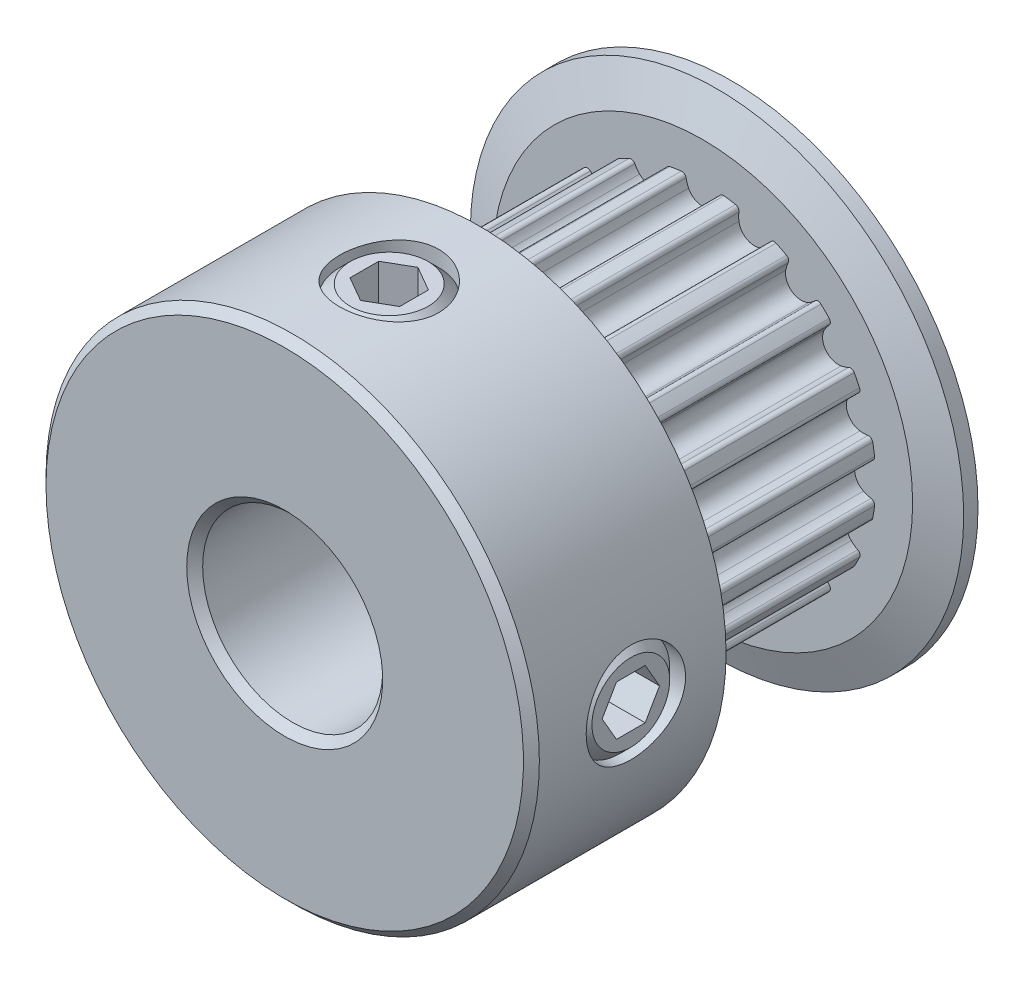
SolidWorks part; units mm, degrees
ref_plane "Front Plane" through (0, 0, 0) normal (0, 0, 1) x (1, 0, 0)
ref_plane "Top Plane" through (0, 0, 0) normal (0, 1, 0) x (1, 0, 0)
ref_plane "Right Plane" through (0, 0, 0) normal (1, 0, 0) x (0, 0, -1)
sketch "Sketch1" plane through (0, 0, 0) normal (0, 0, 1) x (1, 0, 0)
  line L1 (-1.7499, 5.3585) -> (1.7499, 5.3585) construction
  line L4 (0, 0) -> (0, 5.3585) construction
  line L5 (0, 5.3585) -> (0, 11.2111) construction
  line L6 (0, 6.3625) -> (1.9751, 6.0482) construction
  line L7 (1.9751, 6.0482) -> (2.6648, 5.8229) construction
  line L8 (1.9751, 6.0482) -> (1.7499, 5.3585) construction
  line L9 (-1.9751, 6.0482) -> (-1.7499, 5.3585) construction
  line L10 (-1.8963, 5.8067) -> (-2.841, 8.6995)
  line L11 (-2.841, 8.6995) -> (2.841, 8.6995)
  line L12 (2.841, 8.6995) -> (1.8963, 5.8067)
  circle A0 centre (0, 0) radius 6.3625 construction
  circle A1 centre (0, 0) radius 8.6995 construction
  circle A2 centre (0, 0) radius 6.1085 construction
  arc A3 (-0.4989, 5.6703) -> (0.4989, 5.6703) centre (0, 5.9135) ccw
  arc A4 (-0.4989, 5.6703) -> (-0.5855, 5.9387) centre (0.4, 6.1085) cw
  arc A5 (-1.8963, 5.8067) -> (-0.7518, 6.0621) centre (0, 0) cw
  arc A6 (-0.5855, 5.9387) -> (-0.7518, 6.0621) centre (-0.7333, 5.9132) ccw
  arc A7 (1.8963, 5.8067) -> (0.7518, 6.0621) centre (0, 0) ccw
  arc A8 (0.5855, 5.9387) -> (0.7518, 6.0621) centre (0.7333, 5.9132) cw
  arc A9 (0.4989, 5.6703) -> (0.5855, 5.9387) centre (-0.4, 6.1085) ccw
  point P6 (0, 20.9083)
  point P11 (0, 6.3625)
  point P13 (0, 8.6995)
  point P14 (0, 6.1085)
  dimension "D1" = 9.6972
  dimension "D2" = 4.8486
sketch "Sketch2" plane through (0, 0, 0) normal (1, 0, 0) x (0, 0, -1)
  line L0 (-7.875, 3.175) -> (7.875, 3.175)
  line L1 (-7.875, 3.175) -> (-7.875, 8.6995)
  line L2 (-1.01, 8.6995) -> (-7.875, 8.6995)
  line L3 (-1.515, 3.175) -> (-1.515, 8.6995) construction
  line L4 (-1.515, 8.6995) -> (-0.505, 8.6995) construction
  line L5 (-0.505, 8.6995) -> (-0.505, 6.1085) construction
  line L6 (-0.505, 6.1085) -> (6.865, 6.1085)
  line L7 (6.865, 6.1085) -> (6.865, 8.6995) construction
  line L8 (6.865, 8.6995) -> (7.875, 8.6995) construction
  line L9 (7.875, 8.6995) -> (7.875, 3.175)
  line L10 (-7.875, 0) -> (7.875, 0) construction
  line L11 (7.37, 8.6995) -> (6.865, 7.404)
  line L12 (-0.505, 7.404) -> (-1.01, 8.6995)
  line L14 (-0.505, 7.404) -> (-0.505, 6.1085)
  line L15 (6.865, 6.1085) -> (6.865, 7.404)
  line L16 (7.37, 8.6995) -> (7.875, 8.6995)
  arc A0 (-0.505, 7.404) -> (-1.01, 8.6995) centre (-2.4192, 7.404) ccw construction
  arc A1 (6.865, 7.404) -> (7.37, 8.6995) centre (8.7792, 7.404) cw construction
  point P12 (-0.505, 7.404)
  point P14 (-1.01, 8.6995)
  point P20 (6.865, 7.404)
  point P21 (7.37, 8.6995)
  point P25 (6.865, 0)
  point P26 (-0.505, 0)
  dimension "OA" = 15.75
  dimension "Bore" = 6.35
  dimension "Outside Width" = 8.38
  dimension "Inside Width" = 7.37
revolve "Revolve1" add sketch "Sketch2" angle 360 mid plane about L10
sketch "Sketch3" plane through (0, 0, 0) normal (0, 0, 1) x (1, 0, 0)
  line L6 (2.841, 8.6995) -> (-2.841, 8.6995)
  line L7 (1.8963, 5.8067) -> (2.841, 8.6995)
  line L8 (-2.841, 8.6995) -> (-1.8963, 5.8067)
  line L9 (2.841, 8.6995) -> (-2.841, 8.6995)
  line L10 (1.8963, 5.8067) -> (2.841, 8.6995)
  line L11 (-2.841, 8.6995) -> (-1.8963, 5.8067)
  arc A8 (1.8963, 5.8067) -> (0.7518, 6.0621) centre (0, 0) ccw
  arc A9 (0.7518, 6.0621) -> (0.5855, 5.9387) centre (0.7333, 5.9132) ccw
  arc A10 (0.4989, 5.6703) -> (0.5855, 5.9387) centre (-0.4, 6.1085) ccw
  arc A11 (-0.4989, 5.6703) -> (0.4989, 5.6703) centre (0, 5.9135) ccw
  arc A12 (-0.5855, 5.9387) -> (-0.4989, 5.6703) centre (0.4, 6.1085) ccw
  arc A13 (-0.5855, 5.9387) -> (-0.7518, 6.0621) centre (-0.7333, 5.9132) ccw
  arc A14 (-0.7518, 6.0621) -> (-1.8963, 5.8067) centre (0, 0) ccw
  arc A15 (1.8963, 5.8067) -> (0.7518, 6.0621) centre (0, 0) ccw
  arc A16 (0.7518, 6.0621) -> (0.5855, 5.9387) centre (0.7333, 5.9132) ccw
  arc A17 (0.4989, 5.6703) -> (0.5855, 5.9387) centre (-0.4, 6.1085) ccw
  arc A18 (-0.4989, 5.6703) -> (0.4989, 5.6703) centre (0, 5.9135) ccw
  arc A19 (-0.5855, 5.9387) -> (-0.4989, 5.6703) centre (0.4, 6.1085) ccw
  arc A20 (-0.5855, 5.9387) -> (-0.7518, 6.0621) centre (-0.7333, 5.9132) ccw
  arc A21 (-0.7518, 6.0621) -> (-1.8963, 5.8067) centre (0, 0) ccw
  dimension "D1" = 0
extrude "Cut-Extrude1" cut sketch "Sketch3" against normal up to vertex (6.865 mm away) from vertex up to point (0, 6.1085, -6.865) starting at point (0, 6.1085, 0.505)
pattern_circular "CirPattern1" count 20 over 360 about axis through (0, 0, 7.875) along (0, 0, 1) of "Cut-Extrude1"
sketch "Sketch4" plane through (0, 0, 0) normal (1, 0, 0) x (0, -1, 0)
  line L0 (0, -0.505) -> (0, -7.875) construction
  line L1 (-3.175, -7.875) -> (3.175, -7.875) construction
  line L2 (7.404, -0.505) -> (-7.404, -0.505) construction
  circle A0 centre (0, -4.19) radius 1.7526
extrude "Cut-Extrude2" cut sketch "Sketch4" along normal through all
ref_plane "Plane1" through (0, 0, 4.19) normal (0, 0, 1) x (1, 0, 0)
sketch "Sketch5" plane through (0, 0, 4.19) normal (0, 0, 1) x (1, 0, 0)
  line L0 (0, 0) -> (0, 8.6995) construction
  line L1 (3.175, -1.3716) -> (3.175, 0)
  line L2 (3.556, -1.7526) -> (8.1401, -1.7526)
  line L3 (3.175, 0) -> (8.6995, 0) construction
  line L4 (3.175, 0) -> (8.5211, 0)
  line L5 (8.5211, 0) -> (8.5211, -1.3716)
  line L6 (3.556, -1.7526) -> (3.175, -1.3716)
  line L7 (8.5211, -1.3716) -> (8.1401, -1.7526)
  circle A0 centre (0, 0) radius 8.6995 construction
  circle A1 centre (0, 0) radius 3.175 construction
  point P2 (3.175, -1.7526)
  point P11 (8.5211, -1.7526)
revolve "Revolve2" add sketch "Sketch5" angle 360 mid plane about L4
sketch "Sketch6" plane through (8.5211, 5.3841, 0) normal (-1, 0, 0) x (0, -1, 0)
  line L1 (5.3841, 5.2019) -> (4.5078, 4.6959)
  line L2 (4.5078, 4.6959) -> (4.5078, 3.6841)
  line L3 (4.5078, 3.6841) -> (5.3841, 3.1781)
  line L4 (5.3841, 3.1781) -> (6.2604, 3.6841)
  line L5 (6.2604, 3.6841) -> (6.2604, 4.6959)
  line L6 (6.2604, 4.6959) -> (5.3841, 5.2019)
  circle A0 centre (5.3841, 4.19) radius 0.8763 construction
  dimension "D1" = 1.7526
extrude "Cut-Extrude3" cut sketch "Sketch6" along normal blind 1.3144
pattern_circular "CirPattern3" count 2 over 90 about axis through (0, 0, 7.875) along (0, 0, 1) of "Cut-Extrude2", "Revolve2", "Cut-Extrude3"
chamfer "Chamfer1" distance 0.2807 angle 45 2 edges at (3.175, 0, 7.875) (8.6995, 0, 7.875)
ref_axis "Center Axis 1" through (0, 0, -7.875) along (0, 0, 1)
ref_plane "Contact Plane 1" through (0, 0, 7.875) normal (0, 0, 1) x (1, 0, 0)
ref_plane "Contact Plane 2" through (0, 0, -7.875) normal (0, 0, -1) x (-1, 0, 0)
equation "\"D2@Sketch1\"= \"D1@Sketch1\" / 2"
equation "\"D1@Sketch6\" = \"Set Screw@Sketch4\" / 2"
equation "\"D1@Cut-Extrude3\" = \"D1@Sketch6\"*.75"
